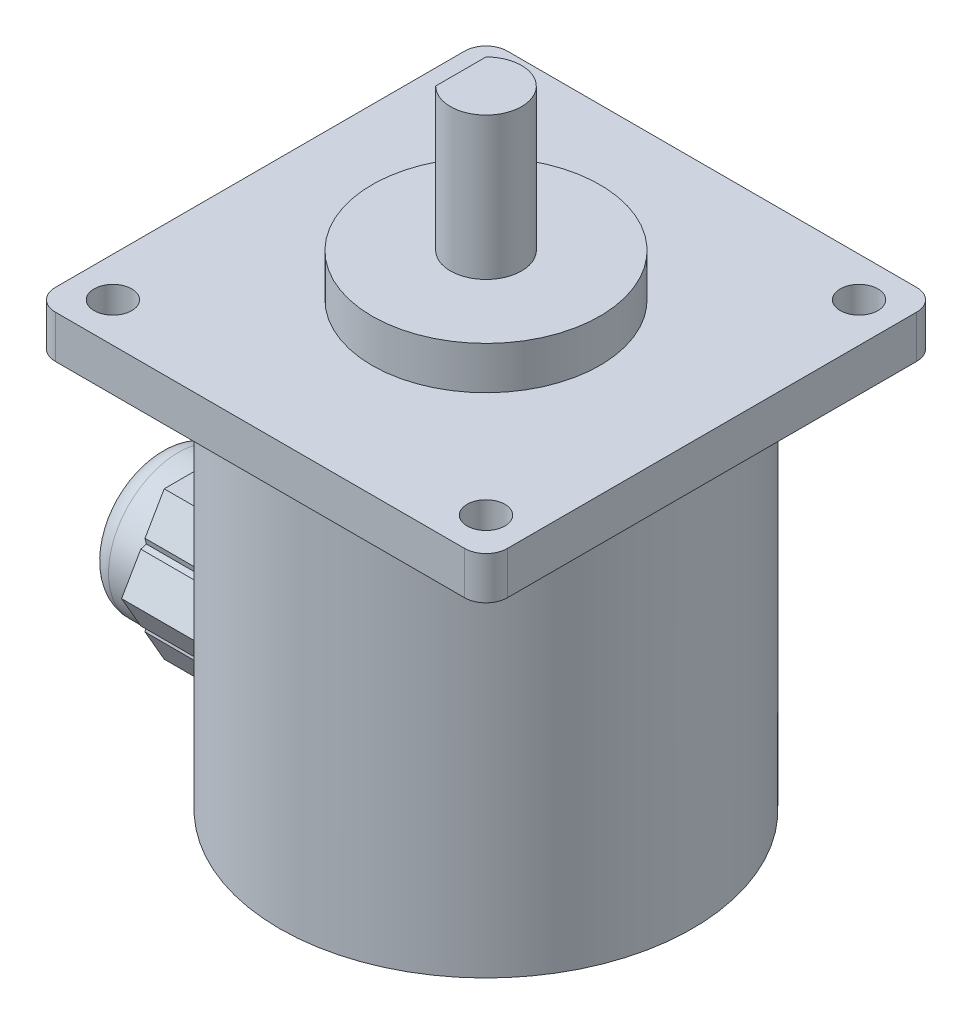
SolidWorks part; units mm, degrees
ref_plane "Front Plane" through (0, 0, 0) normal (0, 0, 1) x (1, 0, 0)
ref_plane "Top Plane" through (0, 0, 0) normal (0, 1, 0) x (1, 0, 0)
ref_plane "Right Plane" through (0, 0, 0) normal (1, 0, 0) x (0, 0, -1)
sketch "Sketch1" plane through (0, 0, 0) normal (0, 1, 0) x (1, 0, 0)
  line L0 (0, 26.2) -> (0, -26.2) construction
  line L1 (-28.75, 31.75) -> (28.75, 31.75)
  line L2 (-31.75, 28.75) -> (-31.75, -28.75)
  line L3 (-28.75, -31.75) -> (28.75, -31.75)
  line L4 (31.75, 28.75) -> (31.75, -28.75)
  line L5 (-31.75, 31.75) -> (31.75, -31.75) construction
  line L6 (-31.75, -31.75) -> (31.75, 31.75) construction
  line L7 (-26.2, 0) -> (26.2, 0) construction
  line L9 (-3.5355, -3.5355) -> (-3.5355, 3.5355)
  circle A0 centre (0, 0) radius 16
  circle A1 centre (-26.2, 26.2) radius 2.65
  circle A2 centre (26.2, 26.2) radius 2.65
  circle A3 centre (26.2, -26.2) radius 2.65
  circle A4 centre (-26.2, -26.2) radius 2.65
  arc A5 (-31.75, -28.75) -> (-28.75, -31.75) centre (-28.75, -28.75) ccw
  arc A6 (28.75, -31.75) -> (31.75, -28.75) centre (28.75, -28.75) ccw
  arc A7 (28.75, 31.75) -> (31.75, 28.75) centre (28.75, 28.75) cw
  arc A8 (-28.75, 31.75) -> (-31.75, 28.75) centre (-28.75, 28.75) ccw
  circle A9 centre (0, 0) radius 5
  circle A10 centre (0, 0) radius 29
  point P21 (0, 0)
  dimension "D1" = 4
  dimension "D2" = 3
extrude "Boss-Extrude1" add sketch "Sketch1" along normal blind 32 contours L9 A9 region at (0.4126, 0, 0)
extrude "Boss-Extrude2" add sketch "Sketch1<3>" along normal blind 12 contours L9 A9 | A0 A9 region at (-4.1294, 0, 0) region at (-15.5475, 0, 0)
sketch "Sketch1<3>" plane through (0, 0, 0) normal (0, 1, 0) x (1, 0, 0) same geometry as "Sketch1"
extrude "Boss-Extrude3" add sketch "Sketch1<4>" along normal blind 6 contours A10 A0 | L1 A8 L2 A5 L3 A6 L4 A7 A10 A1 A2 A3 A4 region at (0, 0, -30.852) region at (-28.1798, 0, 0)
sketch "Sketch1<4>" plane through (0, 0, 0) normal (0, 1, 0) x (1, 0, 0) same geometry as "Sketch1"
extrude "Boss-Extrude4" add sketch "Sketch1<5>" against normal blind 56 contours A10 A0 | A0 A9 | L9 A9 | L9 A9 region at (-4.1294, 0, 0) region at (0.4126, 0, 0) region at (-15.5475, 0, 0) region at (-28.1798, 0, 0)
sketch "Sketch1<5>" plane through (0, 0, 0) normal (0, 1, 0) x (1, 0, 0) same geometry as "Sketch1"
sketch3d "3DSketch1"
  point P0 (-28.8695, -39.897, -2.7477)
ref_plane "Plane1" through (-28.8695, 0, 0) normal (-1, 0, 0) x (0, 0, 1)
sketch "Sketch2" plane through (-28.8695, 0, 0) normal (-1, 0, 0) x (0, 0, 1)
  line L0 (-1.6554, 0.0837) -> (-1.6554, -56) construction
  line L1 (-29, -56) -> (29, -56) construction
  line L2 (-1.6554, -56) -> (-1.6554, -45.6328) construction
  line L3 (-1.6554, -45.6328) -> (7.3229, -50.8164) construction
  line L4 (4.3301, -56) -> (10.3156, -45.6328)
  line L5 (10.3156, -45.6328) -> (4.3301, -35.2656)
  line L6 (4.3301, -35.2656) -> (-7.6409, -35.2656)
  line L7 (-7.6409, -35.2656) -> (-13.6264, -45.6328)
  line L8 (-13.6264, -45.6328) -> (-7.6409, -56)
  line L9 (-7.6409, -56) -> (4.3301, -56)
  line L10 (6.8386, -50.5368) -> (7.0269, -51.3291)
  line L11 (6.8386, -50.5368) -> (7.6189, -50.3037)
  line L12 (6.8386, -50.5368) -> (7.0269, -51.3291)
  line L13 (6.8386, -50.5368) -> (7.6189, -50.3037)
  line L14 (-1.6554, -55.4408) -> (-1.0634, -56)
  line L15 (-1.6554, -55.4408) -> (-2.2474, -56)
  line L16 (-1.6554, -45.6328) -> (-1.6554, -56) construction
  line L17 (-10.1494, -50.5368) -> (-10.3377, -51.3291)
  line L18 (-10.1494, -50.5368) -> (-10.9296, -50.3037)
  line L19 (-1.6554, -45.6328) -> (-10.6336, -50.8164) construction
  line L20 (-10.1494, -40.7288) -> (-10.9296, -40.9619)
  line L21 (-10.1494, -40.7288) -> (-10.3377, -39.9365)
  line L22 (-1.6554, -45.6328) -> (-10.6336, -40.4492) construction
  line L23 (-1.6554, -35.8247) -> (-2.2474, -35.2656)
  line L24 (-1.6554, -35.8247) -> (-1.0634, -35.2656)
  line L25 (-1.6554, -45.6328) -> (-1.6554, -35.2656) construction
  line L26 (6.8386, -40.7288) -> (7.0269, -39.9365)
  line L27 (6.8386, -40.7288) -> (7.6189, -40.9619)
  line L28 (-1.6554, -45.6328) -> (7.3229, -40.4492) construction
  circle A0 centre (-1.6554, -45.6328) radius 10.3672 construction
  point P39 (-1.6554, -45.6328)
  dimension "D1" = 6
extrude "Boss-Extrude5" add sketch "Sketch2" along normal blind 12 and the other way blind 5 contours L27 L26 L5 L6 L24 L23 L7 L21 L20 L8 L18 L17 L9 L15 L14 L4 L10 L11 region at (-28.8695, -45.6328, -1.6554)
sketch "Sketch3" plane through (-40.8695, 0, 0) normal (-1, 0, 0) x (0, 0, 1)
  line L0 (-1.6554, -35.8247) -> (-1.6554, -55.4408) construction
  circle A0 centre (-1.6554, -45.6328) radius 9.8081
extrude "Boss-Extrude6" add sketch "Sketch3" along normal blind 7
fillet "Fillet1" radius 3 1 edges at (-47.8695, -55.4408, -1.6554)
